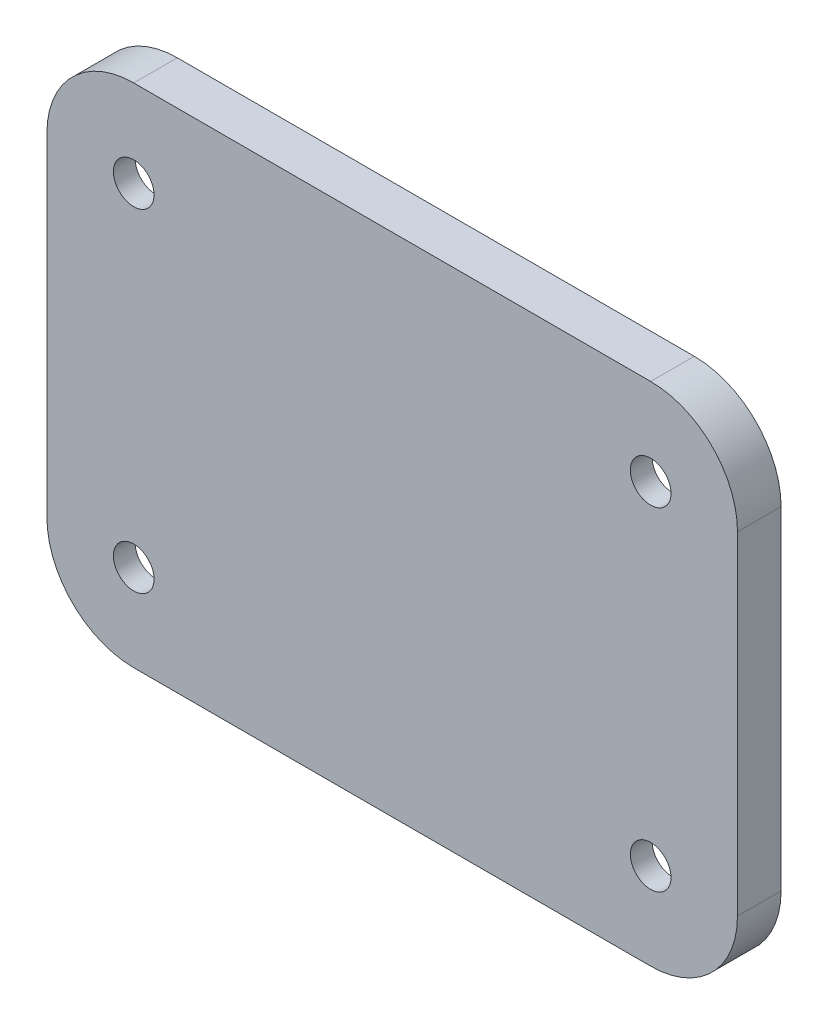
SolidWorks part; units mm, degrees
ref_plane "Front Plane" through (0, 0, 0) normal (0, 0, 1) x (1, 0, 0)
ref_plane "Top Plane" through (0, 0, 0) normal (0, 1, 0) x (1, 0, 0)
ref_plane "Right Plane" through (0, 0, 0) normal (1, 0, 0) x (0, 0, -1)
sketch "Sketch1" plane through (0, 0, 0) normal (0, 0, 1) x (1, 0, 0)
  line L4 (-17.7875, 11.45) -> (-17.7875, 17.425) construction
  line L5 (23.7625, -17.425) -> (-23.7625, -17.425)
  line L6 (23.7625, -17.425) -> (23.7625, 17.425)
  line L7 (23.7625, 17.425) -> (-23.7625, 17.425)
  line L8 (-22.275, 11.45) -> (-22.275, -11.45)
  line L9 (-18.1222, -15.925) -> (18.1222, -15.925)
  line L10 (22.275, -11.45) -> (22.275, 11.45)
  line L11 (18.1222, 15.925) -> (-18.1222, 15.925)
  line L12 (-22.275, 11.45) -> (-22.275, -11.45)
  line L13 (-18.1222, -15.925) -> (18.1222, -15.925)
  line L14 (22.275, -11.45) -> (22.275, 11.45)
  line L15 (18.1222, 15.925) -> (-18.1222, 15.925)
  line L16 (-23.7625, -17.425) -> (-23.7625, 17.425)
  line L17 (23.7625, -17.425) -> (-23.7625, 17.425) construction
  line L18 (23.7625, 17.425) -> (-23.7625, -17.425) construction
  line L19 (-17.7875, 11.45) -> (-23.7625, 11.45) construction
  circle A0 centre (-17.7875, 11.45) radius 1.4
  circle A1 centre (-17.7875, 11.45) radius 1.4 construction
  circle A2 centre (17.7875, 11.45) radius 1.4
  circle A3 centre (17.7875, 11.45) radius 1.4 construction
  circle A4 centre (17.7875, -11.45) radius 1.4
  circle A5 centre (17.7875, -11.45) radius 1.4 construction
  circle A6 centre (-17.7875, -11.45) radius 1.4
  circle A7 centre (-17.7875, -11.45) radius 1.4 construction
  circle A8 centre (-17.7875, 11.45) radius 5.975
  circle A9 centre (17.7875, 11.45) radius 5.975
  circle A10 centre (17.7875, -11.45) radius 5.975
  circle A11 centre (-17.7875, -11.45) radius 5.975
  arc A16 (22.275, 11.45) -> (18.1222, 15.925) centre (17.7875, 11.45) ccw
  arc A17 (22.275, 11.45) -> (18.1222, 15.925) centre (17.7875, 11.45) ccw
  arc A18 (-18.1222, 15.925) -> (-22.275, 11.45) centre (-17.7875, 11.45) ccw
  arc A19 (-18.1222, 15.925) -> (-22.275, 11.45) centre (-17.7875, 11.45) ccw
  arc A20 (-22.275, -11.45) -> (-18.1222, -15.925) centre (-17.7875, -11.45) ccw
  arc A21 (-22.275, -11.45) -> (-18.1222, -15.925) centre (-17.7875, -11.45) ccw
  arc A22 (18.1222, -15.925) -> (22.275, -11.45) centre (17.7875, -11.45) ccw
  arc A23 (18.1222, -15.925) -> (22.275, -11.45) centre (17.7875, -11.45) ccw
  point P24 (0, 0)
  dimension "D2" = 1.5
  dimension "D1" = 0.25
extrude "Boss-Extrude1" add sketch "Sketch1" along normal blind 1.5 contours L15 A19 L12 A8 A0 | A19 L15 A8 L12 | A11 L12 A8 L16 | A21 L12 A11 L13 | L12 A21 L13 A11 A6 | A11 L13 A10 L14 A9 L15 A8 L12 | A9 L7 A8 L15 | A17 L14 A9 L15 | L14 A17 L15 A9 A2 | L13 A23 L14 A10 A4 | A10 L6 A9 L14 | A23 L13 A10 L14 | A11 L5 A10 L13 region at (0, -16.7008, 0) region at (15.7203, -16.9061, 0) region at (23.0626, 0, 0) region at (-21.9132, -15.5757, 0) region at (13.6736, -7.3231, 0) region at (0, 0, 0) region at (23.2469, 9.3915, 0) region at (-23.0626, 0, 0) region at (-15.9753, -15.7771, 0) region at (0, 16.7008, 0) region at (13.6736, 7.3231, 0) region at (-21.9132, 15.5757, 0) region at (-22.1271, 9.4775, 0)
sketch "Sketch2" plane through (0, 0, 0) normal (0, 0, -1) x (-1, 0, 0)
  line L0 (17.7875, 15.925) -> (-17.7875, 15.925)
  line L1 (-22.2625, 11.45) -> (-22.2625, -11.45)
  line L2 (-17.7875, -15.925) -> (17.7875, -15.925)
  line L3 (22.2625, -11.45) -> (22.2625, 11.45)
  line L4 (-17.7875, -17.425) -> (17.7875, -17.425)
  line L5 (-23.7625, 11.45) -> (-23.7625, -11.45)
  line L6 (17.7875, 17.425) -> (-17.7875, 17.425)
  line L7 (23.7625, -11.45) -> (23.7625, 11.45)
  line L8 (-17.7875, -17.425) -> (17.7875, -17.425)
  line L9 (-23.7625, 11.45) -> (-23.7625, -11.45)
  line L10 (17.7875, 17.425) -> (-17.7875, 17.425)
  line L11 (23.7625, -11.45) -> (23.7625, 11.45)
  arc A0 (22.2625, 11.45) -> (17.7875, 15.925) centre (17.7875, 11.45) ccw
  arc A1 (-17.7875, 15.925) -> (-22.2625, 11.45) centre (-17.7875, 11.45) ccw
  arc A2 (-22.2625, -11.45) -> (-17.7875, -15.925) centre (-17.7875, -11.45) ccw
  arc A3 (17.7875, -15.925) -> (22.2625, -11.45) centre (17.7875, -11.45) ccw
  arc A4 (-23.7625, -11.45) -> (-17.7875, -17.425) centre (-17.7875, -11.45) ccw
  arc A5 (-17.7875, 17.425) -> (-23.7625, 11.45) centre (-17.7875, 11.45) ccw
  arc A6 (23.7625, 11.45) -> (17.7875, 17.425) centre (17.7875, 11.45) ccw
  arc A7 (17.7875, -17.425) -> (23.7625, -11.45) centre (17.7875, -11.45) ccw
  arc A8 (-23.7625, -11.45) -> (-17.7875, -17.425) centre (-17.7875, -11.45) ccw
  arc A9 (-17.7875, 17.425) -> (-23.7625, 11.45) centre (-17.7875, 11.45) ccw
  arc A10 (23.7625, 11.45) -> (17.7875, 17.425) centre (17.7875, 11.45) ccw
  arc A11 (17.7875, -17.425) -> (23.7625, -11.45) centre (17.7875, -11.45) ccw
  dimension "D2" = 1.5
  dimension "D1" = 0
extrude "Boss-Extrude2" add sketch "Sketch2" along normal blind 1.5
sketch "Sketch3" plane through (0, 0, 0) normal (0, 0, -1) x (-1, 0, 0)
  line L0 (-22.2625, 11.45) -> (-22.2625, -11.45) construction
  line L1 (22.2625, -6.975) -> (-22.2625, -6.975)
  line L2 (22.2625, -6.975) -> (22.2625, 6.975)
  line L3 (22.2625, 6.975) -> (-22.2625, 6.975)
  line L4 (-22.2625, -6.975) -> (-22.2625, 6.975)
  line L5 (22.2625, -6.975) -> (-22.2625, 6.975) construction
  line L6 (22.2625, 6.975) -> (-22.2625, -6.975) construction
  line L7 (17.7875, 15.925) -> (-17.7875, 15.925) construction
  line L8 (-13.3125, -15.925) -> (13.3125, -15.925)
  line L9 (-13.3125, -15.925) -> (-13.3125, 15.925)
  line L10 (-13.3125, 15.925) -> (13.3125, 15.925)
  line L11 (13.3125, -15.925) -> (13.3125, 15.925)
  line L12 (-13.3125, -15.925) -> (13.3125, 15.925) construction
  line L13 (-13.3125, 15.925) -> (13.3125, -15.925) construction
  circle A0 centre (17.7875, 11.45) radius 4.475
  arc A1 (22.2625, 11.45) -> (17.7875, 15.925) centre (17.7875, 11.45) ccw construction
  circle A2 centre (-17.7875, 11.45) radius 4.475
  circle A3 centre (-17.7875, -11.45) radius 4.475
  circle A4 centre (17.7875, -11.45) radius 4.475
  point P0 (0, 0)
  point P8 (0, 0)
  line M3 (22.2625, -11.45) -> (22.2625, 11.45)
  line M5 (17.7875, 15.925) -> (-17.7875, 15.925)
  line M7 (-22.2625, 11.45) -> (-22.2625, -11.45)
  line M9 (-17.7875, -15.925) -> (17.7875, -15.925)
extrude "Cut-Extrude1" cut sketch "Sketch3" against normal blind 0.5 contours A2 L3 L9 | L1 L9 L3 M7 | L3 L11 L9 M5 | A0 L11 L3 | L11 L1 L3 M3 | A4 L1 L11 | L11 L1 L9 M9 | L1 L11 L3 L9 region at (-17.7875, 0, 0) region at (-14.3121, -7.9746, 0) region at (0, -11.45, 0) region at (0, 0, 0) region at (-14.3121, 7.9746, 0) region at (17.7875, 0, 0) region at (0, 11.45, 0) region at (14.3121, 7.9746, 0)
sketch "Sketch4" plane through (0, 0, 1.5) normal (0, 0, 1) x (1, 0, 0)
  circle A0 centre (-17.7875, 11.45) radius 3
  circle A1 centre (17.7875, 11.45) radius 3
  circle A2 centre (17.7875, -11.45) radius 3
  circle A3 centre (-17.7875, -11.45) radius 3
  dimension "D1" = 6
extrude "Cut-Extrude2" [suppressed] cut sketch "Sketch4" against normal blind 0.4
chamfer "Chamfer1" [suppressed] distance 1.2 angle 45
